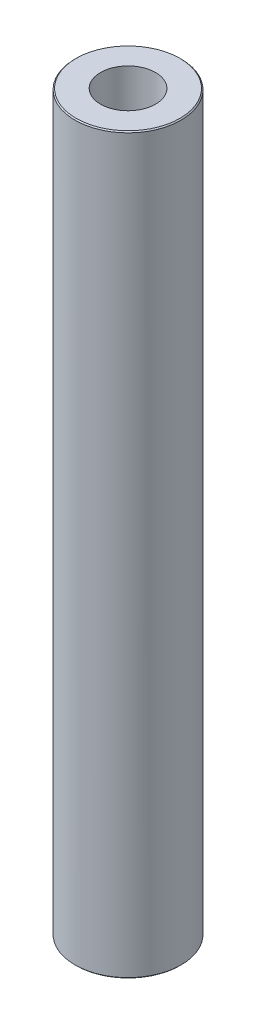
SolidWorks part; units mm, degrees
ref_plane "Front Plane" through (0, 0, 0) normal (0, 0, 1) x (1, 0, 0)
ref_plane "Top Plane" through (0, 0, 0) normal (0, 1, 0) x (1, 0, 0)
ref_plane "Right Plane" through (0, 0, 0) normal (1, 0, 0) x (0, 0, -1)
sketch "Sketch1" plane through (0, 0, 0) normal (0, 1, 0) x (1, 0, 0)
  circle A0 centre (0, 0) radius 17.5
  dimension "SHAFT_OD" = 35
extrude "Boss-Extrude1" add sketch "Sketch1" along normal blind 242.1295
sketch "Sketch2" plane through (0, 0, 0) normal (0, 1, 0) x (1, 0, 0)
  circle A0 centre (0, 0) radius 9.0756
  dimension "BORE_D" = 18.1512
extrude "Cut-Extrude1" cut sketch "Sketch2" along normal through all
chamfer "Chamfer1" distance 0.3561 angle 45.166 2 edges at (0, 242.1295, 17.5) (0, 0, 17.5) first distance on face at (0, 242.1295, 17.5) first distance on face at (0, 0, 9.0756)
